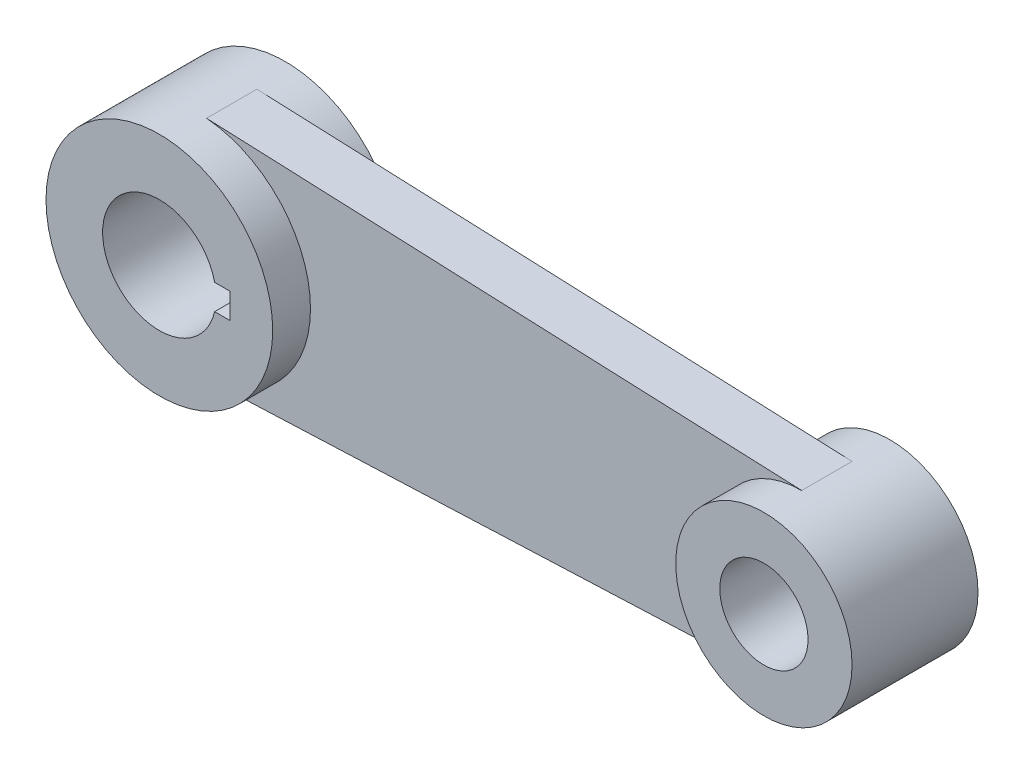
SolidWorks part; units mm, degrees
ref_plane "Front Plane" through (0, 0, 0) normal (0, 0, 1) x (1, 0, 0)
ref_plane "Top Plane" through (0, 0, 0) normal (0, 1, 0) x (1, 0, 0)
ref_plane "Right Plane" through (0, 0, 0) normal (1, 0, 0) x (0, 0, -1)
sketch "Sketch1" plane through (0, 0, 0) normal (0, 0, 1) x (1, 0, 0)
  line L0 (0, 0) -> (35, 0) construction
  line L1 (0, -6.3) -> (35, -6.3)
  line L2 (0, 6.3) -> (35, 6.3)
  line L3 (35, 6.3) -> (35, -6.3)
  arc A0 (27.436, 6.3) -> (27.436, -6.3) centre (0, 0) ccw
  circle A1 centre (0, 0) radius 56.25
  circle A2 centre (300, 0) radius 21.9
  circle A3 centre (300, 0) radius 43.75
  point P12 (0, 0)
  dimension "D1" = 87.5
  dimension "D2" = 43.8
  dimension "D3" = 112.5
  dimension "D4" = 56.3
  dimension "D5" = 300
  dimension "D6" = 6.3
  dimension "D8" = 35
  dimension "D7" = 6.3
extrude "Boss-Extrude1" add sketch "Sketch1" along normal mid plane 62.5 contours A1 A0 L2 L3 L1 | A3 A2 region at (-54.659, 0, 0) region at (257.4874, 0, 0)
sketch "Sketch2" plane through (0, 0, 0) normal (0, 0, 1) x (1, 0, 0)
  line L0 (0, 56.25) -> (300, 43.75)
  line L1 (0, -56.25) -> (300, -43.75)
  circle A0 centre (300, 0) radius 43.75 construction
  circle A1 centre (0, 0) radius 56.25 construction
  arc A2 (300, 43.75) -> (300, -43.75) centre (300, 0) ccw
  arc A3 (0, -56.25) -> (0, 56.25) centre (0, 0) ccw
extrude "Boss-Extrude2" add sketch "Sketch2" along normal mid plane 25 contours A3 L1 A2 L0 region at (152.0048, 0, 0)
